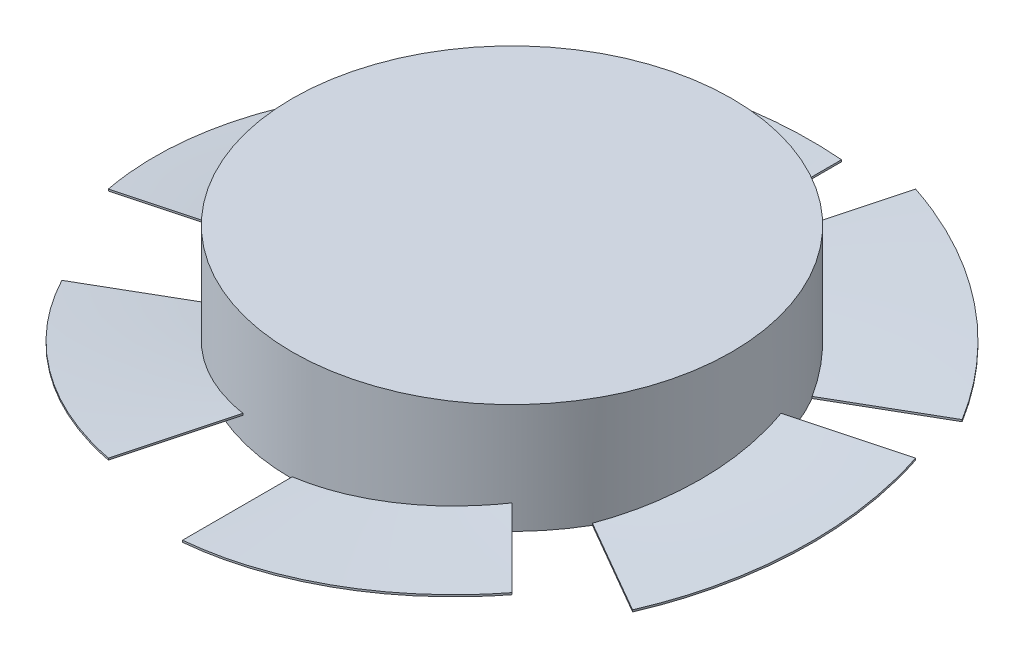
SolidWorks part; units mm, degrees
ref_plane "Front Plane" through (0, 0, 0) normal (0, 0, 1) x (1, 0, 0)
ref_plane "Top Plane" through (0, 0, 0) normal (0, 1, 0) x (1, 0, 0)
ref_plane "Right Plane" through (0, 0, 0) normal (1, 0, 0) x (0, 0, -1)
sketch "Sketch6" plane through (0, 0, 0) normal (0, 1, 0) x (1, 0, 0)
  circle A0 centre (0, 0) radius 12
  dimension "D1" = 24
extrude "Boss-Extrude2" add sketch "Sketch6" along normal blind 6
sketch "Sketch7" plane through (0, 0, 0) normal (0, 1, 0) x (1, 0, 0)
  circle A0 centre (0, 0) radius 12
curve "Helix/Spiral2" pitch 10 height 1.25 radius 12 centre (0, 0, 0) axis (0, 1, 0) start towards (0, 0, 1)
sketch "Sketch8" plane through (0, 0, 0) normal (1, 0, 0) x (0, 0, -1)
  line L1 (-12, 0) -> (-18, 0)
  line L2 (-12, 0) -> (-12, 0.1)
  line L3 (-12, 0.1) -> (-18, 0.1)
  line L4 (-18, 0) -> (-18, 0.1)
  dimension "D1" = 0.1
  dimension "D2" = 6
sweep "Sweep2" add profiles "Sketch8" path "Helix/Spiral2"
ref_axis "Axis1" through (0, 6.3, 0) along (0, -1, 0)
pattern_circular "CirPattern1" count 6 over 360 about axis through (0, 6.3, 0) along (0, -1, 0) of "Sweep2", "Boss-Extrude2"
